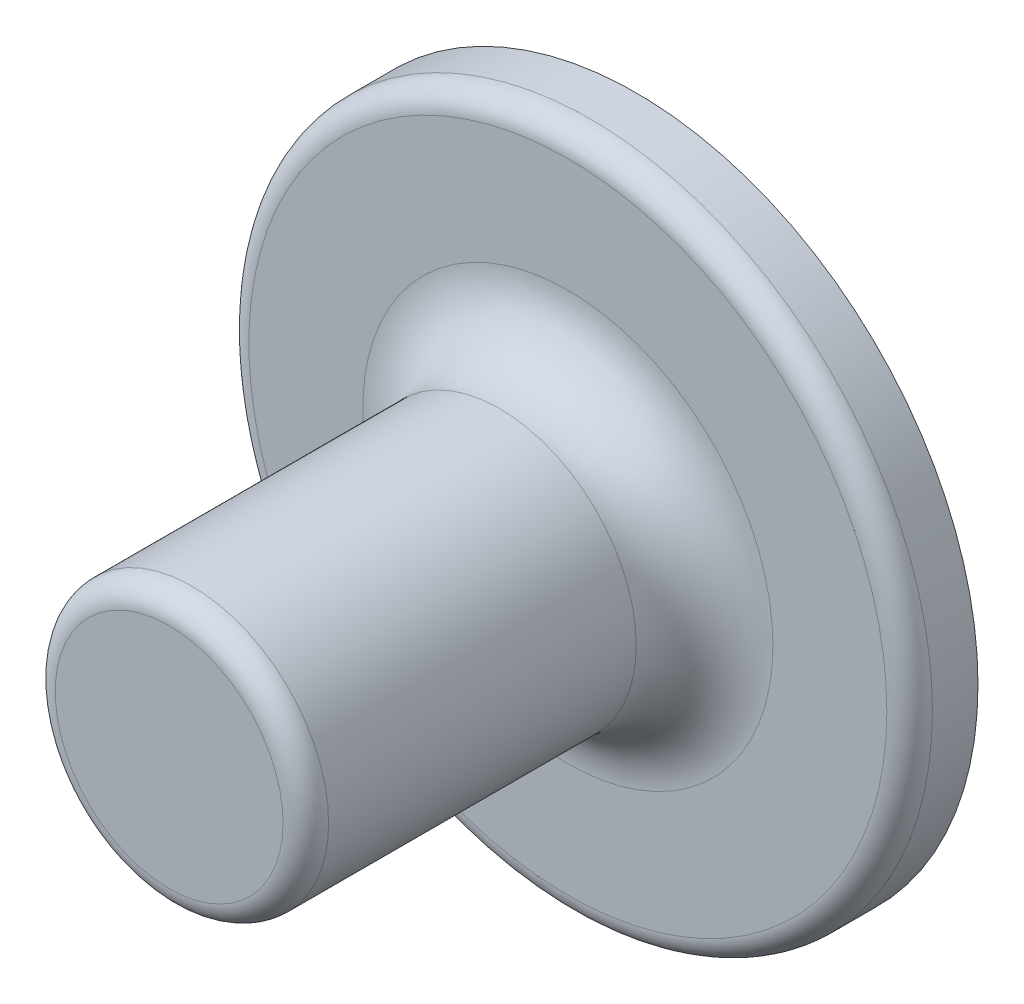
SolidWorks part; units mm, degrees
ref_plane "前视基准面" through (0, 0, 0) normal (0, 0, 1) x (1, 0, 0)
ref_plane "上视基准面" through (0, 0, 0) normal (0, 1, 0) x (1, 0, 0)
ref_plane "右视基准面" through (0, 0, 0) normal (1, 0, 0) x (0, 0, -1)
other "Configuration Table"
sketch "草图1" plane through (0, 0, 0) normal (0, 0, 1) x (1, 0, 0)
  circle A0 centre (0, 0) radius 15
  dimension "D1" = 30
extrude "凸台-拉伸1" add sketch "草图1" along normal blind 3
sketch "草图2" plane through (0, 0, 3) normal (0, 0, 1) x (1, 0, 0)
  circle A0 centre (0, 0) radius 6
  dimension "D1" = 12
extrude "凸台-拉伸2" add sketch "草图2" along normal blind 17.5
fillet "圆角1" radius 3 1 edges at (6, 0, 3)
fillet "圆角2" radius 1 1 edges at (15, 0, 3)
fillet "圆角3" radius 1 1 edges at (6, 0, 20.5)
